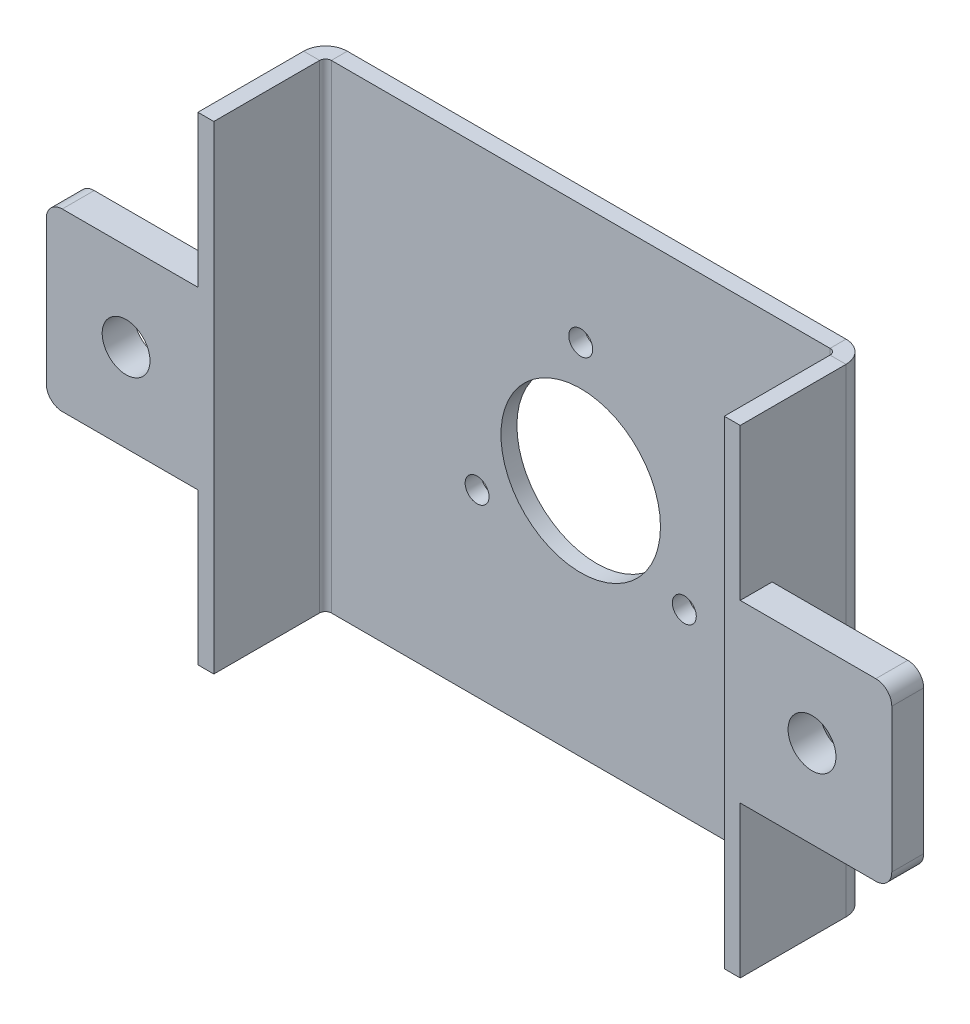
SolidWorks part; units mm, degrees
note: The reader was unsure of these and kept them because the rebuilt part matched: flange length of "Edge-Flange1".
ref_plane "Front Plane" through (0, 0, 0) normal (0, 0, 1) x (1, 0, 0)
ref_plane "Top Plane" through (0, 0, 0) normal (0, 1, 0) x (1, 0, 0)
ref_plane "Right Plane" through (0, 0, 0) normal (1, 0, 0) x (0, 0, -1)
sketch "Sketch1" plane through (0, 0, 0) normal (0, 0, 1) x (1, 0, 0)
  line L1 (-32, -30) -> (32, -30)
  line L2 (-32, -30) -> (-32, 30)
  line L3 (-32, 30) -> (32, 30)
  line L4 (32, -30) -> (32, 30)
  line L5 (-32, -30) -> (32, 30) construction
  line L6 (-32, 30) -> (32, -30) construction
  point P0 (0, 0)
  dimension "D1" = 60
  dimension "D2" = 64
base flange "Base-Flange1" sketch "Sketch1" thickness 2 reverse thickness direction no parameters "D1"=0.7366
edge flange "Edge-Flange1" sketch "Sketch10" flange profiles "Sketch10", "Sketch11" flange angle 90 flange length 14 flange position material outside bend radius 0.7366 thickness 2 relief rectangular parameters "D6"=10, "D8"=1
sketch "Sketch10" plane through (-32, 0, 0) normal (-1, 0, 0) x (0, -1, 0)
  line L2 (-30, 0) -> (-30, 14)
  line L3 (-30, 14) -> (30, 14)
  line L4 (30, 14) -> (30, 0)
  line L5 (-30, 0) -> (30, 0) construction
  line L6 (-30, 0) -> (30, 0)
sketch "Sketch11" plane through (32, 0, 0) normal (1, 0, 0) x (0, 1, 0)
  line L2 (-30, 0) -> (-30, 14)
  line L3 (-30, 14) -> (30, 14)
  line L4 (30, 14) -> (30, 0)
  line L5 (-30, 0) -> (30, 0) construction
  line L6 (-30, 0) -> (30, 0)
bend "EdgeBend1" bend radius 0.7366 bend angle 90 parameters "D5"=1
bend "EdgeBend2" bend radius 0.7366 bend angle 90 parameters "D5"=2
sketch "Sketch12" plane through (-34, 0, 0) normal (-1, 0, 0) x (0, 0, 1)
  line L0 (14, -30) -> (14, 30) construction
  line L1 (10, 11) -> (14, 11)
  line L2 (10, 11) -> (10, -11)
  line L3 (10, -11) -> (14, -11)
  line L4 (14, 11) -> (14, -11)
  line L5 (10, 11) -> (14, -11) construction
  line L6 (10, -11) -> (14, 11) construction
  line L7 (8.8, 0) -> (-8.8, 0) construction
  point P0 (12, 0)
  dimension "D1" = 22
  dimension "D2" = 4
extrude "Boss-Extrude1" add sketch "Sketch12" along normal blind 19
fillet "Fillet1" radius 2 2 edges at (-53, -11, 12) (-53, 11, 12)
mirror "Mirror1" about plane through (0, 0, 0) normal (1, 0, 0) of "Fillet1", "Boss-Extrude1"
hole_wizard "Ø6.0mm Dowel Hole1" positions "Sketch18" profile "Sketch17" hole size "Ø6.0" standard "ANSI Metric"
sketch "Sketch18" plane through (0, 0, 10) normal (0, 0, -1) x (-1, 0, 0)
  point P0 (-43, 0)
  point P2 (43, 0)
  dimension "D1" = 86
  dimension "D2" = 43
sketch "Sketch17" plane through (43, 0, 10) normal (1, 0, 0) x (0, 1, 0)
  line L0 (0, 0) -> (0, 13.8026)
  line L1 (0, 13.8026) -> (3, 12)
  line L2 (3, 12) -> (3, 0)
  line L5 (3, 0) -> (0, 0)
  line L10 (0, 13.8026) -> (-3, 12) construction
  line L11 (0, -6.35) -> (0, 107.95) construction
  dimension "Hole Dia." = 6
  dimension "Hole Depth" = 12
  dimension "Drill Angle" = 118
sketch "Sketch19" plane through (0, 0, 0) normal (0, 0, 1) x (1, 0, 0)
  circle A0 centre (0, 0) radius 10
  dimension "D1" = 20
extrude "Cut-Extrude1" cut sketch "Sketch19" against normal up to next normal cut yes
hole_wizard "Ø3.0mm Dowel Hole1" positions "Sketch21" profile "Sketch20" hole size "Ø3.0" standard "ANSI Metric"
sketch "Sketch21" plane through (0, 0, 0) normal (0, 0, 1) x (1, 0, 0)
  point P0 (0, 15)
  dimension "D1" = 15
sketch "Sketch20" plane through (0, 15, 0) normal (1, 0, 0) x (0, -1, 0)
  line L0 (0, 0) -> (0, 12.9013)
  line L1 (0, 12.9013) -> (1.5, 12)
  line L2 (1.5, 12) -> (1.5, 0)
  line L5 (1.5, 0) -> (0, 0)
  line L10 (0, 12.9013) -> (-1.5, 12) construction
  line L11 (0, -6.35) -> (0, 107.95) construction
  dimension "Hole Dia." = 3
  dimension "Hole Depth" = 12
  dimension "Drill Angle" = 118
pattern_circular "CirPattern1" count 3 over 360 about axis through (0, 0, 0) along (0, 0, 1) of "Ø3.0mm Dowel Hole1"
sketch "Bend-Lines1" plane through (0, 0, 0) normal (0, 1, 0) x (1, 0, 0)
sketch "Bounding-Box1" plane through (0, 0, 0) normal (0, 1, 0) x (1, 0, 0)
sheet metal parameters "Sheet-Metal(1)" thickness 2 parameters "D1"=0.7366
flat pattern "Flat-Pattern(1)" [suppressed]
sketch "Bend-Lines2" plane through (0, 0, 0) normal (0, 1, 0) x (1, 0, 0)
sketch "Bounding-Box2" [suppressed] plane through (0, 0, 0) normal (0, 1, 0) x (1, 0, 0)
sheet metal parameters "Sheet-Metal(2)" thickness 2 parameters "D1"=0.7366
flat pattern "Flat-Pattern(1)" [suppressed]
sketch "Bend-Lines2" plane through (0, 0, 0) normal (0, 1, 0) x (1, 0, 0)
sketch "Bounding-Box2" [suppressed] plane through (0, 0, 0) normal (0, 1, 0) x (1, 0, 0)
bend of the flat pattern "Flatten-<EdgeBend1>1"
bend of the flat pattern "Flatten-<EdgeBend2>1"
sheet metal parameters "Sheet-Metal(3)" thickness 2 parameters "D1"=0.7366
flat pattern "Flat-Pattern(1)" [suppressed]
sketch "Bend-Lines2" plane through (0, 0, 0) normal (0, 1, 0) x (1, 0, 0)
sketch "Bounding-Box2" [suppressed] plane through (0, 0, 0) normal (0, 1, 0) x (1, 0, 0)
bend of the flat pattern "Flatten-<EdgeBend1>1"
bend of the flat pattern "Flatten-<EdgeBend2>1"
sheet metal parameters "Sheet-Metal(4)" thickness 2 parameters "D1"=0.7366
flat pattern "Flat-Pattern(1)" [suppressed]
sketch "Bend-Lines2" plane through (0, 0, 0) normal (0, 1, 0) x (1, 0, 0)
sketch "Bounding-Box2" [suppressed] plane through (0, 0, 0) normal (0, 1, 0) x (1, 0, 0)
bend of the flat pattern "Flatten-<EdgeBend1>1"
bend of the flat pattern "Flatten-<EdgeBend2>1"
sheet metal parameters "Sheet-Metal(5)" thickness 2 parameters "D1"=0.7366
flat pattern "Flat-Pattern(1)" [suppressed]
sketch "Bend-Lines2" plane through (0, 0, 0) normal (0, 1, 0) x (1, 0, 0)
sketch "Bounding-Box2" [suppressed] plane through (0, 0, 0) normal (0, 1, 0) x (1, 0, 0)
bend of the flat pattern "Flatten-<EdgeBend1>1"
bend of the flat pattern "Flatten-<EdgeBend2>1"
sheet metal parameters "Sheet-Metal(6)" thickness 2 parameters "D1"=0.7366
flat pattern "Flat-Pattern(1)" [suppressed]
sketch "Bend-Lines2" plane through (0, 0, 0) normal (0, 1, 0) x (1, 0, 0)
sketch "Bounding-Box2" [suppressed] plane through (0, 0, 0) normal (0, 1, 0) x (1, 0, 0)
bend of the flat pattern "Flatten-<EdgeBend1>1"
bend of the flat pattern "Flatten-<EdgeBend2>1"
sheet metal parameters "Sheet-Metal(7)" thickness 2 parameters "D1"=0.7366
flat pattern "Flat-Pattern(1)" [suppressed]
sketch "Bend-Lines2" plane through (0, 0, 0) normal (0, 1, 0) x (1, 0, 0)
sketch "Bounding-Box2" [suppressed] plane through (0, 0, 0) normal (0, 1, 0) x (1, 0, 0)
bend of the flat pattern "Flatten-<EdgeBend1>1"
bend of the flat pattern "Flatten-<EdgeBend2>1"
sheet metal parameters "Sheet-Metal(8)" thickness 2 parameters "D1"=0.7366
flat pattern "Flat-Pattern(1)" [suppressed]
sketch "Bend-Lines2" plane through (0, 0, 0) normal (0, 1, 0) x (1, 0, 0)
sketch "Bounding-Box2" [suppressed] plane through (0, 0, 0) normal (0, 1, 0) x (1, 0, 0)
bend of the flat pattern "Flatten-<EdgeBend1>1"
bend of the flat pattern "Flatten-<EdgeBend2>1"
